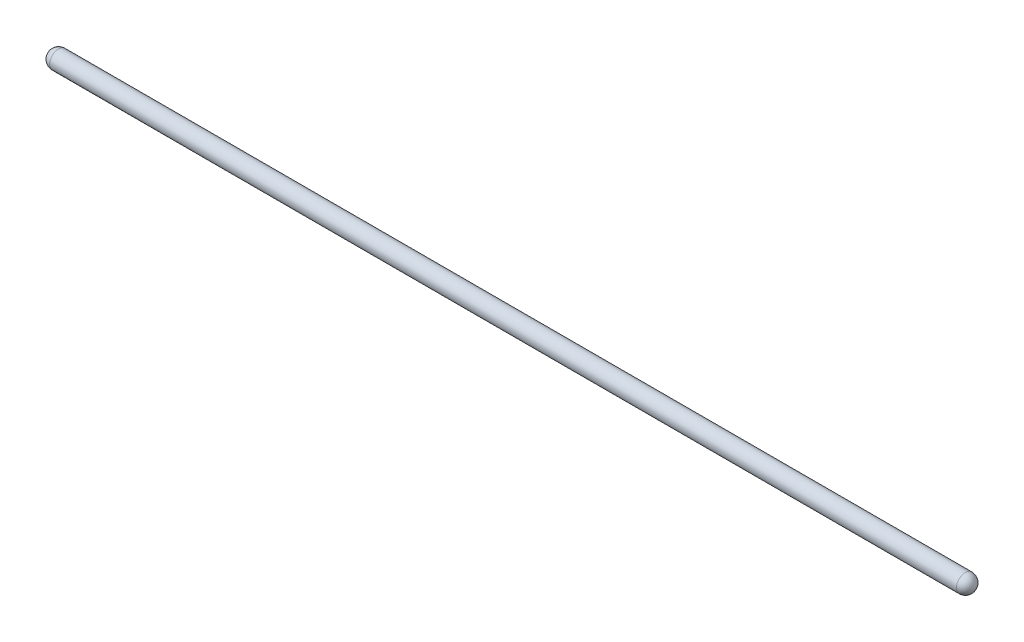
SolidWorks part; units mm, degrees
material "Brass"
ref_plane "Front Plane" through (0, 0, 0) normal (0, 0, 1) x (1, 0, 0)
ref_plane "Top Plane" through (0, 0, 0) normal (0, 1, 0) x (1, 0, 0)
ref_plane "Right Plane" through (0, 0, 0) normal (1, 0, 0) x (0, 0, -1)
sketch "Sketch1" plane through (0, 0, 0) normal (0, 0, 1) x (1, 0, 0)
  line L0 (0, 0) -> (310, 0) construction
  line L1 (3, 3) -> (307, 3)
  line L2 (310, 0) -> (0, 0)
  arc A0 (310, 0) -> (307, 3) centre (307, 0) ccw
  arc A1 (3, 3) -> (0, 0) centre (3, 0) ccw
revolve "Revolve1" add sketch "Sketch1" angle 360 about L0
